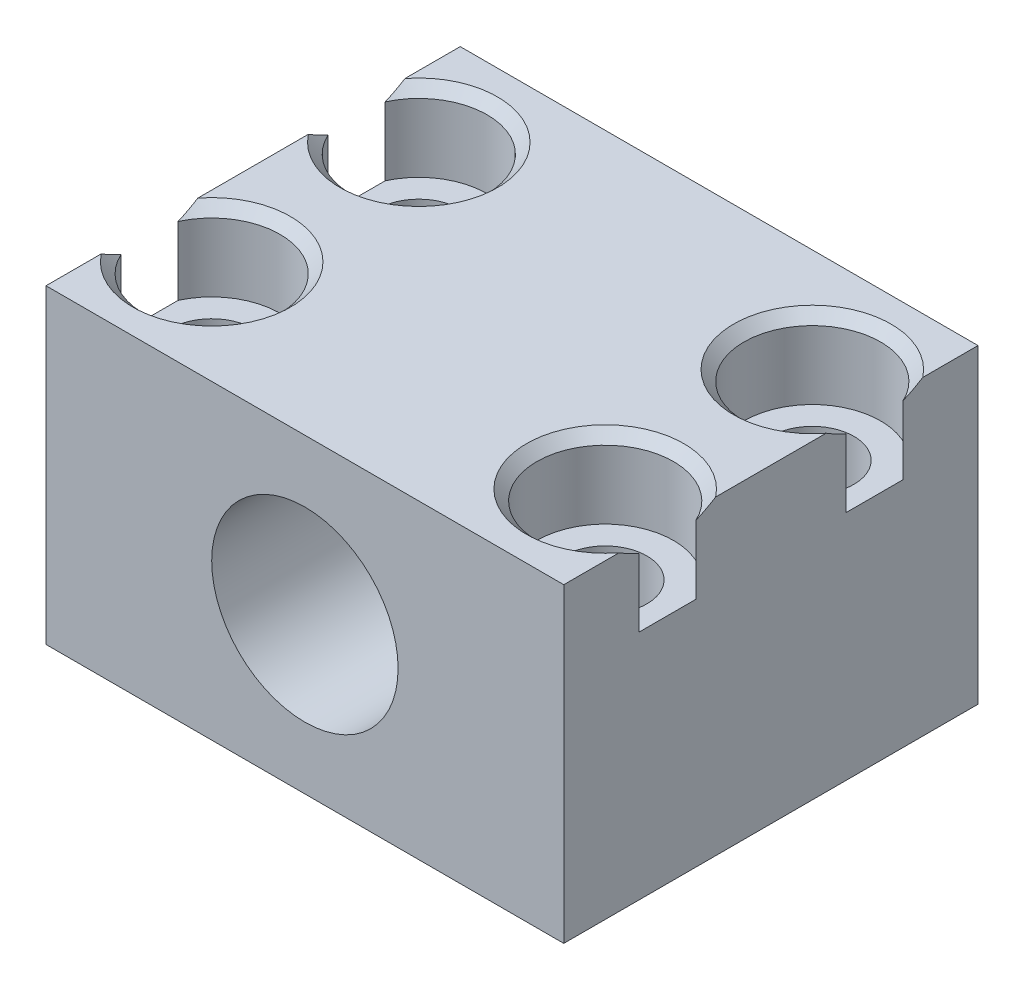
SolidWorks part; units mm, degrees
material "Brass"
ref_plane "Front Plane" through (0, 0, 0) normal (0, 0, 1) x (1, 0, 0)
ref_plane "Top Plane" through (0, 0, 0) normal (0, 1, 0) x (1, 0, 0)
ref_plane "Right Plane" through (0, 0, 0) normal (1, 0, 0) x (0, 0, -1)
sketch "Sketch1" plane through (0, 0, 0) normal (0, 0, 1) x (1, 0, 0)
  circle A0 centre (0, 0) radius 5.715
  circle A1 centre (0, 0) radius 18.669
  dimension "D3" = 11.43
  dimension "D1" = 37.338
extrude "nut-body-extrude" add sketch "Sketch1" along normal blind 25.4
sketch "Sketch2" plane through (0, 0, 0) normal (0, 0, 1) x (1, 0, 0)
  line L0 (0, 9.525) -> (0, 34.8179) construction
  line L1 (9.525, 0) -> (42.4926, 0) construction
  line L3 (-15.875, 9.525) -> (15.875, 9.525)
  line L4 (-15.875, 9.525) -> (-15.875, -9.525)
  line L5 (-15.875, -9.525) -> (15.875, -9.525)
  line L6 (15.875, 9.525) -> (15.875, -9.525)
  circle A1 centre (0, 0) radius 18.669
  circle A2 centre (0, 0) radius 18.669
  point P8 (-15.875, 0)
  point P9 (0, 9.525)
  dimension "D1" = 19.05
  dimension "D3" = 31.75
  dimension "D2" = 0
extrude "nut-trim-cut-extrude" cut sketch "Sketch2" along normal through all contours L3 A2 | L5 A2 | L6 A2 | L4 A2 region at (-18.141, 0, 0)
hole_wizard "CBORE for #10 Socket Head Cap Screw1" positions "Sketch5" profile "Sketch4" counterbore size "#10" standard "ANSI Inch" end condition through all
sketch "Sketch5" plane through (0, 9.525, 0) normal (0, 1, 0) x (1, 0, 0)
  line L0 (12.065, -6.35) -> (12.065, -19.05) construction
  line L1 (12.065, -19.05) -> (-12.065, -19.05) construction
  line L2 (-12.065, -19.05) -> (-12.065, -6.35) construction
  line L3 (-12.065, -6.35) -> (12.065, -6.35) construction
  line L4 (0, 0) -> (0, -12.7) construction
  line L5 (0, -12.7) -> (15.875, -12.7) construction
  line L6 (15.875, -25.4) -> (15.875, 0) construction
  line L7 (-5.715, 0) -> (-5.715, -25.4) construction
  line L8 (-5.715, 0) -> (-5.715, -25.4) construction
  line L9 (5.715, 0) -> (5.715, -25.4) construction
  point P0 (12.065, -6.35)
  point P2 (12.065, -19.05)
  point P4 (-12.065, -19.05)
  point P6 (-12.065, -6.35)
  point P29 (12.065, -12.7)
  point P43 (0, -6.35)
  dimension "D1" = 24.13
  dimension "D2" = 12.7
sketch "Sketch4" plane through (12.065, 9.525, 6.35) normal (1, 0, 0) x (0, 0, 1)
  line L0 (0, 0) -> (0, 19.05)
  line L1 (0, 19.05) -> (2.5527, 19.05)
  line L3 (2.5527, 19.05) -> (2.5527, 4.826)
  line L4 (4.191, 4.826) -> (2.5527, 4.826)
  line L5 (4.191, 4.826) -> (4.191, 0.635)
  line L6 (4.191, 0.635) -> (4.826, 0)
  line L7 (4.826, 0) -> (0, 0)
  line L8 (-4.191, 0.635) -> (-4.826, 0) construction
  line L11 (0, -6.35) -> (0, 107.95) construction
  dimension "Thru Hole Dia." = 5.1054
  dimension "Thru Hole Depth" = 19.05
  dimension "C'Bore Dia." = 8.382
  dimension "C'Bore Depth" = 4.826
  dimension "Near C'Sink Dia." = 9.652
  dimension "Near C'Sink Angle" = 90
equation "\"dovetail-angle\" = 55"
equation "\"dovetail-stock-width\" = 5"
equation "\"dovetail-stock-height\" = 1.25"
equation "\"dovetail-depth\" = 0.5 * \"dovetail-stock-height\""
equation "\"dovetail-throat-width\" = \"dovetail-stock-width\" - (2 * \"dovetail-depth\")"
equation "\"delta-x\" = 6"
equation "\"delta-y\" = 3"
equation "\"gib-thickness\" = 0.25"
equation "\"x-slide-length\" = \"dovetail-stock-width\" + \"delta-x\""
equation "\"y-slide-length\" = \"dovetail-stock-width\" + \"delta-y\""
equation "\"dog-point-diam\" = .149"
equation "\"dog-point-length\" = .067"
equation "\"dovetail-double-height\" = 2 * \"dovetail-depth\" + 0.5"
equation "\"acme-major-diam\" = .5"
equation "\"acme-pitch-diam\" = 0.45"
equation "\"acme-minor-diam\" = 0.4"
equation "\"acme-nut-od\" = 1.47"
equation "\"acme-nut-length\" = 1"
equation "\"D3@Sketch1\"=\"acme-pitch-diam\""
equation "\"D1@Sketch1\"=\"acme-nut-od\""
equation "\"D1@nut-body-extrude\"=\"acme-nut-length\""
equation "\"acme-nut-trim-height\" = .75"
equation "\"D1@Sketch2\"=\"acme-nut-trim-height\""
equation "\"screw-bearing-od\" = 0.5"
equation "\"screw-bearing-length\" = .25"
equation "\"screw-bearing-id\" = .375"
equation "\"end-plate-thickness\" = \"screw-bearing-length\""
equation "\"screw-add-length\" = 2 * \"end-plate-thickness\" + 1 + 0.5"
equation "\"x-screw-length\" = \"x-slide-length\" + \"screw-add-length\""
equation "\"y-screw-length\" = \"y-slide-length\" + \"screw-add-length\""
equation "\"acme-nut-mount-hole-space-vert\" = 0.5 * \"acme-nut-length\""
equation "\"D2@Sketch5\"=\"acme-nut-mount-hole-space-vert\""
equation "\"vise-hole-center-dist\" = 6.75"
equation "\"wiper_plate_clearance\" = .03"
equation "\"dial-width\" = 0.5"
equation "\"quarter-twenty-free-fit\" = .2667"
equation "\"acme-nut-mount-hole-space-horz\" = 0.95"
equation "\"D1@Sketch5\"=\"acme-nut-mount-hole-space-horz\""
